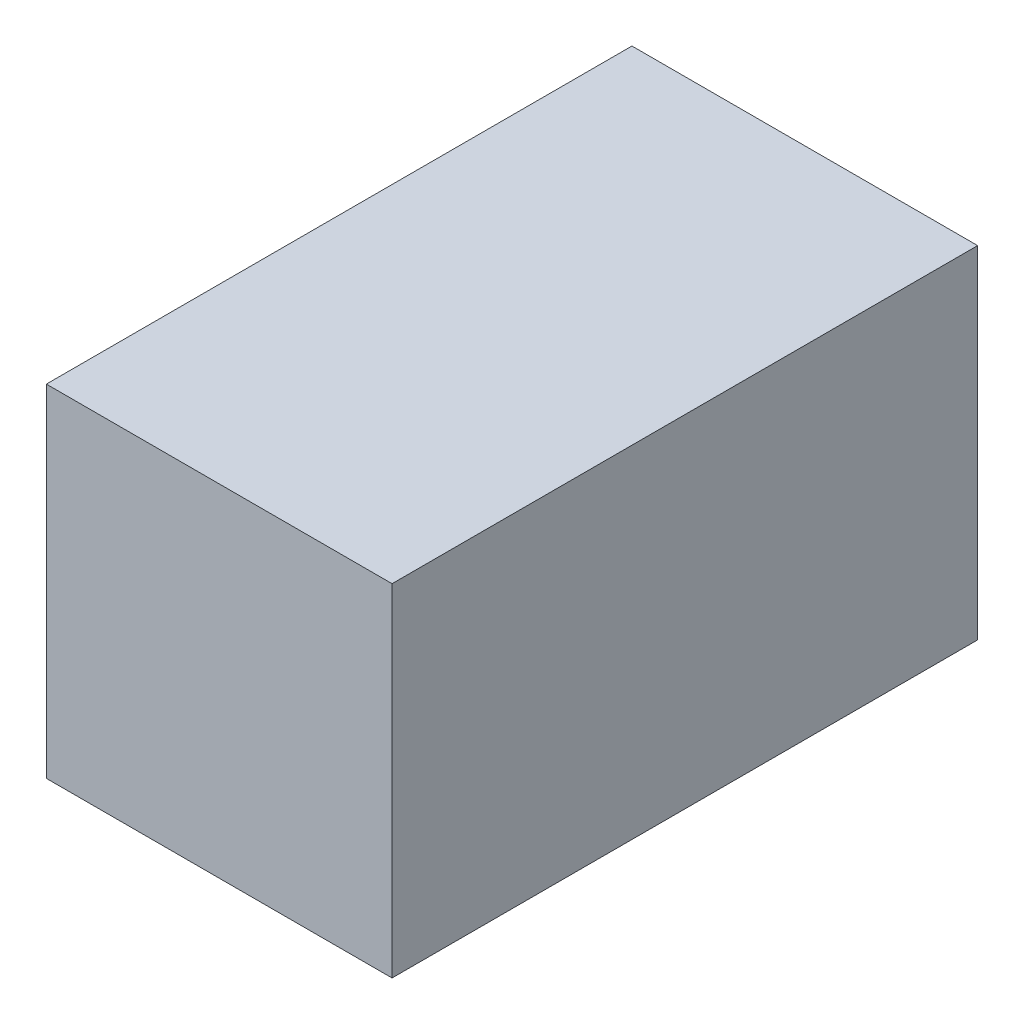
SolidWorks part; units mm, degrees
material "Custom Plastic"
ref_plane "X-Y Datum" through (0, 0, 0) normal (0, 0, 1) x (1, 0, 0)
ref_plane "X-Z Datum" through (0, 0, 0) normal (0, 1, 0) x (1, 0, 0)
ref_plane "Y-Z Datum" through (0, 0, 0) normal (1, 0, 0) x (0, 0, -1)
sketch "Sketch1" plane through (0, 0, 0) normal (0, 0, 1) x (1, 0, 0)
  line L1 (-36.5125, 36.068) -> (36.5125, 36.068)
  line L2 (-36.5125, 36.068) -> (-36.5125, -36.068)
  line L3 (-36.5125, -36.068) -> (36.5125, -36.068)
  line L4 (36.5125, 36.068) -> (36.5125, -36.068)
  line L5 (-36.5125, 36.068) -> (36.5125, -36.068) construction
  line L6 (-36.5125, -36.068) -> (36.5125, 36.068) construction
  circle A0 centre (0, -23.608) radius 8.388 construction
  point P0 (0, 0)
  point P8 (0, -23.608)
  dimension "D1" = 73.025
  dimension "D2" = 72.136
extrude "Boss-Extrude1" add sketch "Sketch1" along normal blind 123.698
